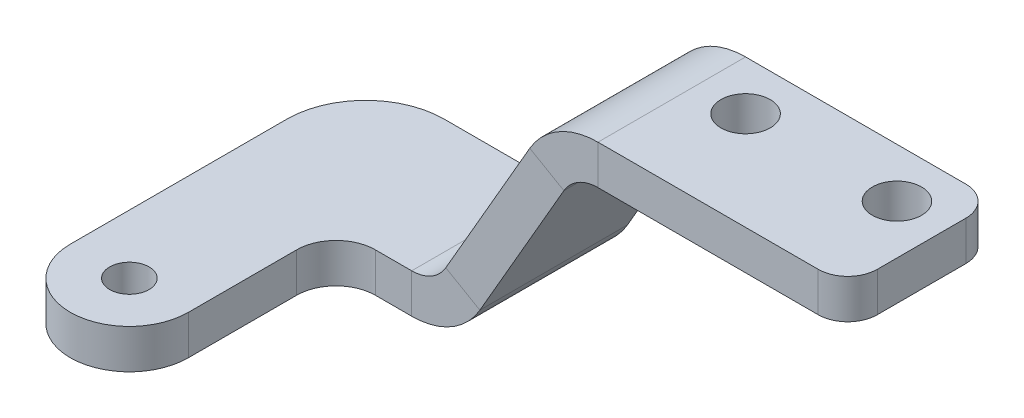
SolidWorks part; units mm, degrees
note: The reader was unsure of these and kept them because the rebuilt part matched: flange length of "Ребро-кромка1", "Ребро-кромка2".
ref_plane "Спереди" through (0, 0, 0) normal (0, 0, 1) x (1, 0, 0)
ref_plane "Сверху" through (0, 0, 0) normal (0, 1, 0) x (1, 0, 0)
ref_plane "Справа" through (0, 0, 0) normal (1, 0, 0) x (0, 0, -1)
sketch "Эскиз1" plane through (0, 0, 0) normal (0, 1, 0) x (1, 0, 0)
  line L0 (4.1151, 33.9749) -> (8.0021, 31.7074) construction
  line L2 (0, 0) -> (-50000, 0) construction
  line L3 (0, 0) -> (0, 50000) construction
  line L4 (-6, 0) -> (-6, 22)
  line L5 (2, 30) -> (16, 30)
  line L6 (16, 30) -> (16, 15)
  line L7 (16, 15) -> (10, 15)
  line L8 (6, 11) -> (6, 0)
  circle A0 centre (0, 0) radius 2
  arc A1 (-6, 0) -> (6, 0) centre (0, 0) ccw
  arc A2 (2, 30) -> (-6, 22) centre (2, 22) ccw
  arc A3 (10, 15) -> (6, 11) centre (10, 11) ccw
  point P5 (0, -6)
  dimension "D1" = 4
  dimension "D3" = 6
  dimension "D6" = 8
  dimension "D5" = 15
  dimension "D2" = 10
  dimension "D4" = 36
base flange "Базовая кромка1" sketch "Эскиз1" thickness 4 reverse thickness direction no parameters "D1"=0.7366
edge flange "Ребро-кромка1" sketch "Эскиз10" flange angle 120 flange length 24 flange position material outside bend radius 4 thickness 4 parameters "D6"=10
sketch "Эскиз10" plane through (16, 0, 0) normal (0.866, -0.5, 0) x (0, 0, -1)
  line L2 (15, 0) -> (15, 21.6906)
  line L3 (15, 21.6906) -> (30, 21.6906)
  line L4 (30, 21.6906) -> (30, 0)
  line L7 (15, 0) -> (30, 0) construction
  line L8 (15, 0) -> (30, 0)
bend "EdgeBend1" bend radius 4 bend angle 60 parameters "D5"=1
edge flange "Ребро-кромка2" sketch "Эскиз13" flange angle 120 flange length 30 flange position material outside bend radius 4 thickness 4 parameters "D6"=10
sketch "Эскиз13" plane through (30.3094, 16.7846, 0) normal (0, -1, 0) x (0, 0, -1)
  line L1 (30, 0) -> (15, 0) construction
  line L2 (15, 0) -> (15, 27.6906)
  line L3 (15, 27.6906) -> (30, 27.6906)
  line L4 (30, 27.6906) -> (30, 0)
  line L5 (30, 0) -> (15, 0)
bend "EdgeBend2" bend radius 4 bend angle 60 parameters "D5"=2
fillet "Скругление1" radius 3 1 edges at (58, 18.7846, -15)
fillet "Скругление2" radius 3 1 edges at (58, 18.7846, -30)
sketch "Эскиз14" plane through (0, 20.7846, 0) normal (0, 1, 0) x (1, 0, 0)
  line L0 (68, 22.5) -> (-49932, 22.5) construction
  line L1 (53, 25) -> (53, 30) construction
  line L2 (53, 25) -> (58, 25) construction
  line L3 (64, 25) -> (-49936, 25) construction
  line L4 (58, 18) -> (58, 27)
  line L5 (55, 30) -> (32.6188, 30)
  line L6 (32.6188, 30) -> (32.6188, 15)
  line L7 (32.6188, 15) -> (55, 15)
  line L8 (58, 18) -> (58, 27) construction
  line L9 (55, 30) -> (32.6188, 30) construction
  line L10 (32.6188, 30) -> (32.6188, 15) construction
  line L11 (32.6188, 15) -> (55, 15) construction
  line L12 (37.6188, 25) -> (37.6188, 30) construction
  line L13 (37.6188, 25) -> (32.6188, 25) construction
  circle A1 centre (53, 25) radius 2.5
  arc A2 (58, 27) -> (55, 30) centre (55, 27) ccw
  arc A3 (55, 15) -> (58, 18) centre (55, 18) ccw
  arc A4 (58, 27) -> (55, 30) centre (55, 27) ccw construction
  arc A5 (55, 15) -> (58, 18) centre (55, 18) ccw construction
  circle A6 centre (37.6188, 25) radius 2.5
  point P13 (58, 22.5)
  dimension "D2" = 5
  dimension "D1" = 0
extrude "Вырез-Вытянуть1" cut sketch "Эскиз14" against normal up to next and the other way through all
sketch "Сгиб-Линии1" [suppressed] plane through (0, 0, 0) normal (0, 1, 0) x (1, 0, 0)
sketch "Граничная рамка1" [suppressed] plane through (0, 0, 0) normal (0, 1, 0) x (1, 0, 0)
sheet metal parameters "Листовой металл3" thickness 4 parameters "D1"=0.7366
flat pattern "Развертка3" [suppressed]
sketch "Сгиб-Линии2" plane through (0, 0, 0) normal (0, 1, 0) x (1, 0, 0)
sketch "Граничная рамка2" [suppressed] plane through (0, 0, 0) normal (0, 1, 0) x (1, 0, 0)
sheet metal parameters "Листовой металл4" thickness 4 parameters "D1"=0.7366
flat pattern "Развертка3" [suppressed]
sketch "Сгиб-Линии2" plane through (0, 0, 0) normal (0, 1, 0) x (1, 0, 0)
sketch "Граничная рамка2" [suppressed] plane through (0, 0, 0) normal (0, 1, 0) x (1, 0, 0)
bend of the flat pattern "Плоское состояние-<EdgeBend1>1"
sheet metal parameters "Листовой металл5" thickness 4 parameters "D1"=0.7366
flat pattern "Развертка3" [suppressed]
sketch "Сгиб-Линии2" plane through (0, 0, 0) normal (0, 1, 0) x (1, 0, 0)
sketch "Граничная рамка2" [suppressed] plane through (0, 0, 0) normal (0, 1, 0) x (1, 0, 0)
bend of the flat pattern "Плоское состояние-<EdgeBend1>1"
bend of the flat pattern "Плоское состояние-<EdgeBend2>1"
sheet metal parameters "Листовой металл6" thickness 4 parameters "D1"=0.7366
flat pattern "Развертка3"
sketch "Сгиб-Линии2" plane through (0, 0, 0) normal (0, 1, 0) x (1, 0, 0)
  line L0 (40.1872, 15) -> (40.1872, 30) construction
  line L1 (16.8322, 15) -> (16.8322, 30) construction
  line L2 (40.1872, 15) -> (40.1872, 30) construction
  line L3 (16.8322, 15) -> (16.8322, 30) construction
sketch3d "Граничная рамка2" [suppressed]
  line L0 (-8, -27.9999, 0) -> (66.71, -27.9999, 0) construction
  line L1 (-8, 8, 0) -> (66.71, 8, 0) construction
  line L2 (-8, -27.9999, 0) -> (-8, 8, 0) construction
  line L3 (66.71, -27.9999, 0) -> (66.71, 8, 0) construction
bend of the flat pattern "Плоское состояние-<EdgeBend1>1"
bend of the flat pattern "Плоское состояние-<EdgeBend2>1"
